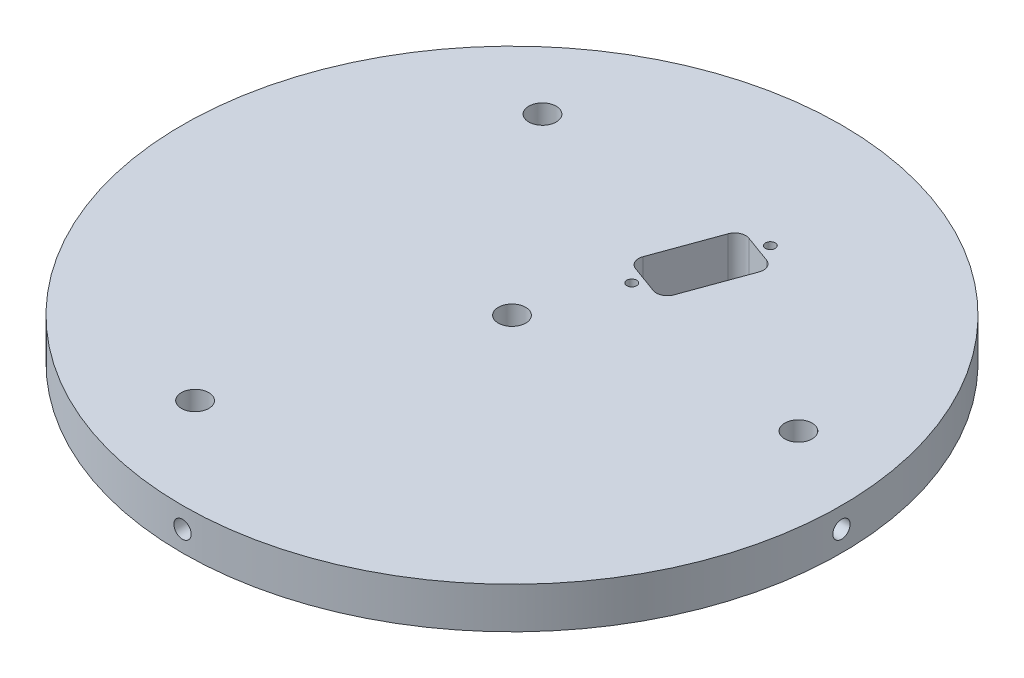
SolidWorks part; units mm, degrees
material "6061-T6 (SS)"
ref_plane "Front Plane" through (0, 0, 0) normal (0, 0, 1) x (1, 0, 0)
ref_plane "Top Plane" through (0, 0, 0) normal (0, 1, 0) x (1, 0, 0)
ref_plane "Right Plane" through (0, 0, 0) normal (1, 0, 0) x (0, 0, -1)
sketch "Sketch1" plane through (0, 0, 0) normal (0, 1, 0) x (1, 0, 0)
  line L0 (0, 0) -> (-50.3682, 60.0265)
  line L1 (0, 0) -> (50.3682, 60.0265)
  line L2 (0, 0) -> (0, 72.1431) construction
  circle A0 centre (0, 0) radius 78.359
  circle A1 centre (0, 0) radius 76.1746
  circle A2 centre (0, 0) radius 76.1746
  dimension "D1" = 156.718
  dimension "D2" = 152.3492
  dimension "D3" = 152.3492
  dimension "D4" = 80
extrude "Boss-Extrude1" add sketch "Sketch1" along normal blind 25.4 contours L2 A2 L1 A0 | L2 A1 L1 A2 | L2 A2 L1 A1 | L2 A0 L1 A2 | A2 L2 A1 L0 | A0 L2 A2 L0 | A2 L2 A0 L0 | A1 L2 A2 L0 region at (0, 0, 13.3592) region at (-23.5316, 0, -29.974) region at (-33.0764, 0, 70.9325) region at (-48.8794, 0, -59.85)
ref_plane "Plane1" through (0, 12.7, 0) normal (0, 1, 0) x (1, 0, 0)
sketch "Sketch6" plane through (0, 25.4, 0) normal (0, 1, 0) x (1, 0, 0)
  circle A0 centre (0, 0) radius 76.1746
  dimension "D1" = 152.3492
extrude "Boss-Extrude5" add sketch "Sketch6" along normal blind 9.525
sketch "Sketch7" plane through (0, 0, 0) normal (0, -1, 0) x (1, 0, 0)
  circle A0 centre (0, 0) radius 76.1746
  dimension "D1" = 152.3492
extrude "Boss-Extrude6" add sketch "Sketch7" along normal blind 9.525
sketch "Sketch8" plane through (0, -9.525, 0) normal (0, -1, 0) x (1, 0, 0)
  circle A0 centre (0, 0) radius 73.025
  dimension "D1" = 146.05
extrude "Cut-Extrude5" cut sketch "Sketch8" against normal up to surface (34.925 mm away) up to face at (0, 25.4, 76.1746)
ref_plane "Plane2" through (0, 0, -76.1746) normal (0, 0, -1) x (-1, 0, 0)
ref_plane "Plane5" through (0, 25.4, 0) normal (0, 1, 0) x (1, 0, 0)
ref_axis "Axis1" through (0, 0, 0) along (0, 1, 0)
sketch "Sketch3" plane through (0, 0, -76.1746) normal (0, 0, -1) x (-1, 0, 0)
  line L4 (76.1746, 0) -> (-76.1746, 0)
  line L5 (-76.1746, -9.525) -> (76.1746, -9.525)
  line L6 (76.1746, 25.4) -> (-76.1746, 25.4)
  line L7 (76.1746, 34.925) -> (-76.1746, 34.925)
  line L8 (0, 34.925) -> (0, 25.4) construction
  line L9 (0, 0) -> (0, -9.525) construction
  circle A0 centre (0, 30.1625) radius 2
  circle A1 centre (0, -4.7625) radius 2
  point P12 (0, 30.1625)
  point P13 (0, -4.7625)
  point P14 (-77.5445, 179.1871)
  dimension "D1" = 4
extrude "Cut-Extrude2" cut sketch "Sketch3" against normal blind 9.525 contours L8 A0 | L8 A0 | L9 A1 | L9 A1 region at (0, 30.1625, -76.1746) region at (0, -4.7625, -76.1746)
extrude "Cut-Extrude3" cut sketch "Sketch1<7>" against normal blind 9.525 from surface contours L2 A1 L1 A2 | A1 L2 A2 L0 | A2 L2 A0 L0 | L2 A2 L1 A0 region at (-23.5316, 0, -29.974) region at (-48.8794, 0, -59.85) starting at plane "Plane5"
sketch "Sketch1<7>" plane through (0, 0, 0) normal (0, 1, 0) x (1, 0, 0) same geometry as "Sketch1"
pattern_circular "CirPattern2" count 3 over 360 about axis through (0, 0, 0) along (0, 1, 0) of "Cut-Extrude3"
ref_plane "Plane3" through (0, 34.925, 0) normal (0, 1, 0) x (1, 0, 0)
sketch "Sketch4" plane through (0, 34.925, 0) normal (0, 1, 0) x (1, 0, 0)
  circle A0 centre (0, 0) radius 73.025
  dimension "D1" = 146.05
extrude "Boss-Extrude4" add sketch "Sketch4" against normal blind 9.525
pattern_circular "CirPattern3" count 4 over 360 about axis through (0, 0, 0) along (0, 1, 0) of "Cut-Extrude2"
sketch "Sketch9" plane through (0, 34.925, 0) normal (0, 1, 0) x (1, 0, 0)
  line L0 (0, 0) -> (-26.8004, -73.6334) construction
  circle A0 centre (0, 0) radius 3.175
  circle A1 centre (-19.5465, -53.7034) radius 3.175
  circle A2 centre (-36.7353, 43.7794) radius 3.175
  circle A3 centre (56.2818, 9.924) radius 3.175
  point P15 (0, 0)
  dimension "D1" = 6.35
  dimension "D2" = 6.35
  dimension "D3" = 57.15
  dimension "D5" = 3
extrude "Cut-Extrude6" cut sketch "Sketch9" against normal through all
sketch "Sketch10" plane through (0, 25.4, 0) normal (0, 1, 0) x (1, 0, 0)
  circle A0 centre (0, 0) radius 82.3228
extrude "Cut-Extrude7" cut sketch "Sketch10" against normal through all
hole_wizard "Tap Drill for #4-40 Tap1" positions "Sketch12" profile "Sketch13" hole size "#4-40" standard "ANSI Inch" end condition through all
sketch "Sketch12" plane through (0, 34.925, 0) normal (0, 1, 0) x (1, 0, 0)
  line L0 (0, 0) -> (18.6243, 51.1699) construction
  line L2 (0, 0) -> (-36.7353, 43.7794) construction
  circle A0 centre (0, 0) radius 21.59 construction
  point P0 (7.3842, 20.288)
  point P2 (15.9347, 43.7803)
  dimension "D3" = 43.18
  dimension "D1" = 60
  dimension "D2" = 25
sketch "Sketch13" plane through (7.3842, 34.925, -20.288) normal (1, 0, 0) x (0, 0, 1)
  line L0 (0, 0) -> (0, 9.525)
  line L1 (0, 9.525) -> (1.1303, 9.525)
  line L2 (1.1303, 9.525) -> (1.1303, 0)
  line L5 (1.1303, 0) -> (0, 0)
  line L11 (0, -6.35) -> (0, 107.95) construction
  dimension "Thru Hole Dia." = 2.2606
  dimension "Thru Hole Depth" = 9.525
sketch "Sketch14" plane through (0, 34.925, 0) normal (0, 1, 0) x (1, 0, 0)
  line L0 (7.3842, 20.288) -> (15.9347, 43.7803) construction
  line L1 (14.6438, 22.7814) -> (19.8932, 37.2038)
  line L2 (11.3883, 21.2633) -> (4.9439, 23.6089)
  line L3 (18.3751, 40.4594) -> (11.9307, 42.8049)
  line L4 (3.4258, 26.8644) -> (8.6751, 41.2868)
  arc A0 (19.8932, 37.2038) -> (18.3751, 40.4594) centre (17.5063, 38.0725) ccw
  arc A1 (11.9307, 42.8049) -> (8.6751, 41.2868) centre (11.0619, 40.4181) ccw
  arc A2 (11.3883, 21.2633) -> (14.6438, 22.7814) centre (12.257, 23.6501) ccw
  arc A3 (4.9439, 23.6089) -> (3.4258, 26.8644) centre (5.8126, 25.9957) cw
  point P0 (8.1661, 22.4361)
  dimension "D4" = 2.54
  dimension "D5" = 2.54
  dimension "D1" = 2.286
  dimension "D2" = 2.286
  dimension "D3" = 11.938
extrude "Cut-Extrude9" cut sketch "Sketch14" against normal through all
equation "\"AB_Coupler_OD_Length\"= 1in"
equation "\"AB_Coupling_Section_Length\"= 0.375in"
equation "\"AB_Coupler_Length\"= \"AB_Coupler_OD_Length\" + \"AB_Coupling_Section_Length\" * 2"
equation "\"Cutout_Angle\" = 80"
equation "\"AB_Coupler_Num_Screws\"= 6"
equation "\"Num_Cutouts\" = 3"
equation "\"AB_Coupler_OD\"= 6.17in"
equation "\"AB_Coupler_ID\"= 5.75in"
equation "\"AB_Coupler_Surface_Diameter\"= 5.998in"
equation "\"D2@Sketch1\"=\"Bodytube_ID\""
equation "\"AB_Coupling_Screw_Diameter\"= 0.1065in"
equation "\"Aft_Section_Length\"= 39in"
equation "\"Aft_Lower_Length\"= 22in"
equation "\"Aft_Upper_Length\"= \"Aft_Section_Length\" - \"Aft_Lower_Length\" - \"AB_Coupler_OD_Length\""
equation "\"Mid_Coupler_Length\"= 13in"
equation "\"Lead_Screw_Dist\" = 2.25in"
equation "\"Lead_Screw_Diam\" = 11mm"
equation "\"Lead_Screw_Length\" = (\"Mid_Coupler_Length\" + 2*0.375in + 2*0.5in)"
equation "\"Bodytube_OD\" = 6.17in"
equation "\"Paddle_Pin_Offset\" = .25in"
equation "\"Bodytube_ID\" = 5.998in"
equation "\"Paddle_Pin_Radius\" = 2.25in"
equation "\"D1@Sketch4\"=\"AB_Coupler_ID\""
equation "\"D1@Sketch6\"=\"AB_Coupler_Surface_Diameter\""
equation "\"D1@Boss-Extrude5\"=\"AB_Coupling_Section_Length\""
equation "\"D1@Sketch7\"=\"AB_Coupler_Surface_Diameter\""
equation "\"D1@Boss-Extrude6\"=\"AB_Coupling_Section_Length\""
equation "\"D1@Sketch8\"=\"AB_Coupler_ID\""
equation "\"D3@Sketch9\"=\"Paddle_Pin_Radius\""
equation "\"Motor_OD\" = 4in"
equation "\"Fwd_Tube_Length\" = 40in"
equation "\"Mid_Tube_Length\" = 1in"
equation "\"AB_Paddle_Height\" = 0.575in"
equation "\"AB_Central_Bushing_Length\" = .75in"
equation "\"Paddle_Gear_OD\" = 3.2in"
equation "\"Fwd_BKHD_From_Top\" = 18in"
equation "\"Fin_Thickness\"= .118in"
equation "\"Guiderail_Cutout_Diameter\"= 1.5in"
equation "\"DB9_Hole_Dist\" = 25mm "
equation "\"D2@Sketch12\"=\"DB9_Hole_Dist\""
